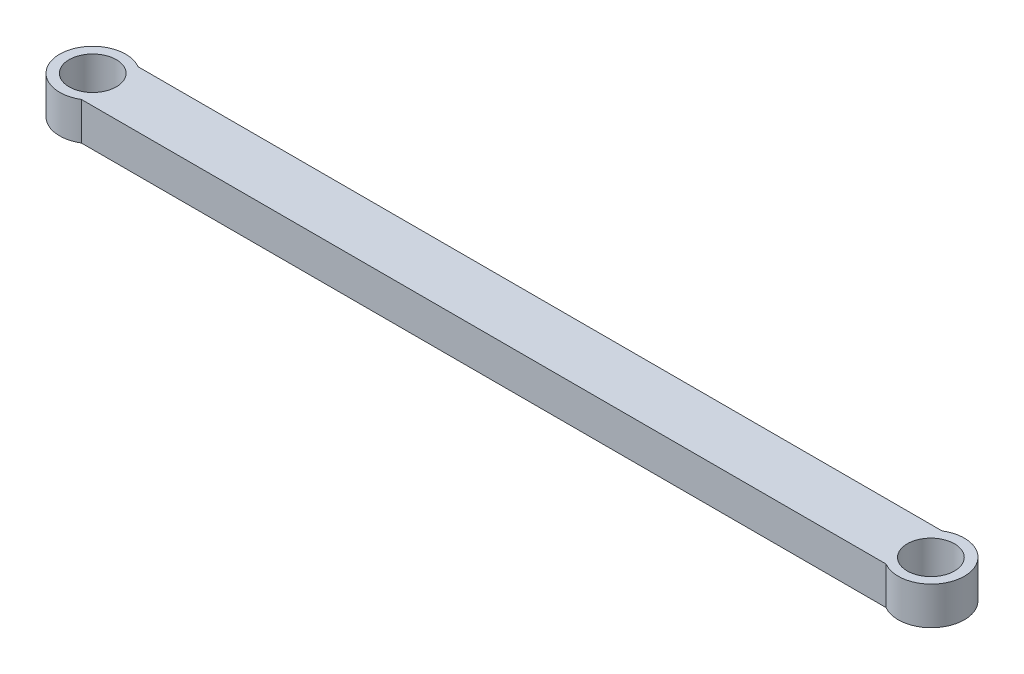
SolidWorks part; units mm, degrees
ref_plane "Front Plane" through (0, 0, 0) normal (0, 0, 1) x (1, 0, 0)
ref_plane "Top Plane" through (0, 0, 0) normal (0, 1, 0) x (1, 0, 0)
ref_plane "Right Plane" through (0, 0, 0) normal (1, 0, 0) x (0, 0, -1)
sketch "Sketch2" plane through (0, 0, 0) normal (0, 1, 0) x (1, 0, 0)
  line L0 (0, 1.75) -> (0, 1.25)
  line L1 (0, -1.25) -> (0, -1.75)
  line L2 (0, 1.5) -> (44.3835, 1.5)
  line L3 (0, -1.5) -> (44.3835, -1.5)
  line L4 (44.3835, 1.7605) -> (44.3835, 1.2395)
  line L5 (44.3835, -1.2605) -> (44.3835, -1.7395)
  circle A0 centre (0, 0) radius 1.75
  circle A1 centre (0, 0) radius 1.25
  circle A2 centre (44.3835, 0.0105) radius 1.75
  circle A3 centre (44.3835, -0.0105) radius 1.25
  point P22 (44.3835, 1.5)
  dimension "D1" = 3.5
  dimension "D3" = 3.5
  dimension "D2" = 0.5
extrude "Boss-Extrude1" add sketch "Sketch2" along normal blind 2 contours A2 L2 A0 L3 | A1 L1 L3 A0 L2 L0 | A1 L0 A0 L1 | A3 L5 A2 L4 | A3 L4 L2 A2 L3 L5 | L2 A0 L0 | L1 A0 L3 | L4 A2 L2 | L3 A2 L5 region at (0.3415, 0, -1.6006) region at (-0.0391, 0, -1.625) region at (0.4507, 0, -1.4653) region at (0.3415, 0, 1.6006) region at (22.1918, 0, 0.0002) region at (44.0353, 0, -1.6049) region at (43.9242, 0, -1.4653) region at (44.0489, 0, 1.5964) region at (44.4226, 0, -1.6303)
sketch "Sketch3" plane through (0, 2, 0) normal (0, 1, 0) x (1, 0, 0)
  circle A0 centre (44.3835, -0.0105) radius 1.25
  circle A1 centre (0, 0) radius 1.25
  dimension "D1" = 2.5
  dimension "D2" = 2.5
